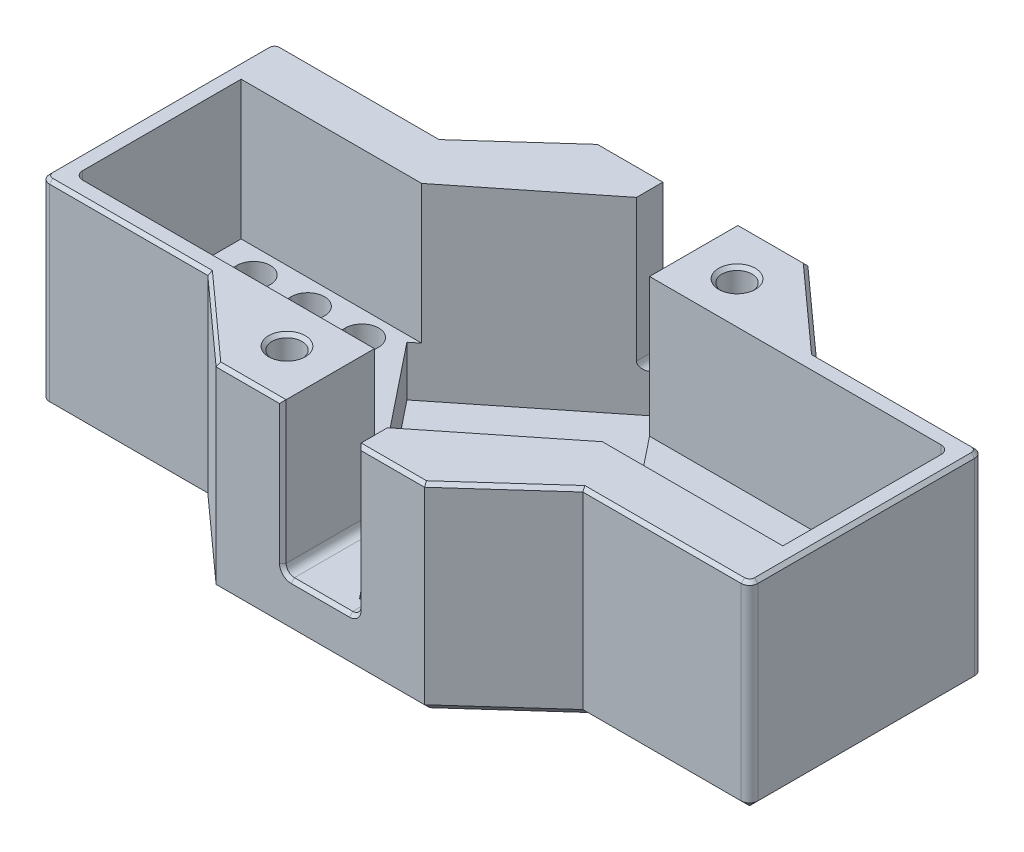
SolidWorks part; units mm, degrees
ref_plane "Front Plane" through (0, 0, 0) normal (0, 0, 1) x (1, 0, 0)
ref_plane "Top Plane" through (0, 0, 0) normal (0, 1, 0) x (1, 0, 0)
ref_plane "Right Plane" through (0, 0, 0) normal (1, 0, 0) x (0, 0, -1)
sketch "Sketch1" plane through (0, 0, 0) normal (0, 1, 0) x (1, 0, 0)
  line L0 (0, 47.9731) -> (0, -55.4983) construction
  line L1 (-64.8003, 0) -> (65.8454, 0) construction
  line L3 (-41.5, 14) -> (41.5, 14)
  line L4 (-42.5, 13) -> (-42.5, -13)
  line L5 (-41.5, -14) -> (41.5, -14)
  line L6 (42.5, 13) -> (42.5, -13)
  arc A0 (41.5, 14) -> (42.5, 13) centre (41.5, 13) cw
  arc A1 (41.5, -14) -> (42.5, -13) centre (41.5, -13) ccw
  arc A2 (-42.5, -13) -> (-41.5, -14) centre (-41.5, -13) ccw
  arc A3 (-41.5, 14) -> (-42.5, 13) centre (-41.5, 13) ccw
  point P11 (42.5, 14)
  point P14 (42.5, -14)
  point P19 (-42.5, 14)
  point P32 (41.5, -11)
  dimension "D3" = 1
  dimension "D1" = 85
  dimension "D2" = 28
extrude "Boss-Extrude2" add sketch "Sketch1" along normal blind 18 and the other way blind 6
sketch "Sketch4" plane through (0, 0, 0) normal (0, 1, 0) x (1, 0, 0)
  line L0 (0, 54.1428) -> (0, -67.8993) construction
  line L1 (-64.1281, 0) -> (64.7051, 0) construction
  line L2 (-12.5, 23) -> (12.5, 23)
  line L3 (12.5, 23) -> (22.5, 14)
  line L4 (41.5, 14) -> (-41.5, 14) construction
  line L6 (-22.5, 14) -> (-12.5, 23)
  line L7 (-22.5, -14) -> (-12.5, -23)
  line L8 (-41.5, -14) -> (41.5, -14) construction
  line L9 (-12.5, -23) -> (12.5, -23)
  line L10 (12.5, -23) -> (22.5, -14)
  line L11 (-22.5, 14) -> (-22.5, -14)
  line L12 (22.5, -14) -> (22.5, 14)
  dimension "D1" = 45
  dimension "D2" = 25
  dimension "D3" = 23
extrude "Boss-Extrude3" add sketch "Sketch4" along normal blind 18 and the other way blind 6
sketch "Sketch5" plane through (0, 0, 0) normal (0, 1, 0) x (1, 0, 0)
  line L1 (-40.5, 8) -> (-40.5, -11.0189)
  line L3 (40.4951, 10.9915) -> (40.4951, -8)
  line L4 (0, 34.3728) -> (0, -34.2865) construction
  line L5 (-53.6508, 0) -> (61.9313, 0) construction
  line L6 (-40.5, 8) -> (-13.5, 8)
  line L7 (-13.5, 8) -> (-13.5, 12)
  line L8 (13.4951, -12) -> (13.4951, -8)
  line L9 (13.4951, -8) -> (40.4951, -8)
  line L10 (-39.5189, -12) -> (13.4951, -12)
  line L11 (-13.5, 12) -> (39.477, 12)
  arc A0 (39.477, 12) -> (40.4951, 10.9915) centre (39.4866, 10.9915) cw
  arc A2 (-40.5, -11.0189) -> (-39.5189, -12) centre (-39.5189, -11.0189) ccw
  point P3 (0, 0)
  point P4 (-18.3724, 10.1)
  point P5 (0, 0)
  point P6 (0, 0)
  point P10 (0, 0)
  dimension "D1" = 12
  dimension "D2" = 80.9951
  dimension "D3" = 24
  dimension "D4" = 4
  dimension "D5" = 4
  dimension "D6" = 27
  dimension "D7" = 27
sketch "Sketch2" plane through (0, 0, 0) normal (0, 0, 1) x (1, 0, 0)
  line L0 (0, 26.5192) -> (0, -25.5049) construction
  line L1 (-24.2779, -6) -> (28.8134, -6) construction
  line L2 (-41.5, -6) -> (-22.5, -6) construction
  line L6 (-3.5, 19) -> (3.5, 19)
  line L9 (-4.5, 18) -> (-4.5, 1)
  line L10 (-3.5, 0) -> (3.5, 0)
  line L11 (4.5, 18) -> (4.5, 1)
  arc A4 (3.5, 0) -> (4.5, 1) centre (3.5, 1) ccw
  arc A5 (-4.5, 1) -> (-3.5, 0) centre (-3.5, 1) ccw
  arc A6 (3.5, 19) -> (4.5, 18) centre (3.5, 18) cw
  arc A7 (-3.5, 19) -> (-4.5, 18) centre (-3.5, 18) ccw
  point P19 (0, 0)
  dimension "D1" = 1
  dimension "D2" = 9
  dimension "D3" = 19
  dimension "D4" = 6
extrude "load bar arm slots" cut sketch "Sketch2" against normal blind 30 and the other way blind 30 contours L9 A5 L10 A4 L11 A6 L6 A7
extrude "10kg TAL bar slot" cut sketch "Sketch5" along normal up to vertex (18 mm away) from offset 1.4 up to point (-41.5, 18, 14)
sketch "Sketch3" plane through (0, 0, 0) normal (0, 1, 0) x (1, 0, 0)
  line L0 (0, 44.5647) -> (0, -57.8829) construction
  line L1 (-55.4498, 0) -> (55.4498, 0) construction
  line L2 (-2.6223, 20.9314) -> (-19.8228, 7.2149)
  line L3 (-19.8228, 7.2149) -> (2.6223, -20.9314)
  line L4 (2.6223, -20.9314) -> (19.8228, -7.2149)
  line L5 (19.8228, -7.2149) -> (-2.6223, 20.9314)
  line L6 (-8.6003, -6.8582) -> (8.6003, 6.8582) construction
  line L7 (-11.2226, 14.0732) -> (11.2226, -14.0732) construction
  point P13 (-4.5, -12)
  point P17 (4.5, 12)
  point P22 (0, 0)
  dimension "D1" = 22
  dimension "D2" = 36
extrude "hx711 chip holster" cut sketch "Sketch3" against normal offset from surface 1.4 and the other way up to vertex (18 mm away) contours L3 L4 L5 L2 up to face at (0, -6, 0) other way up to point (-41.5, 18, 14)
sketch "Sketch6" plane through (0, 0, 0) normal (0, 1, 0) x (1, 0, 0)
  line L0 (0, 33.6156) -> (0, -37.2618) construction
  line L1 (-46.4216, 0) -> (49.9788, 0) construction
  circle A0 centre (-10, -17) radius 1.8
  circle A1 centre (10, 17) radius 1.8
  point P9 (0, 0)
  point P10 (0, 0)
  dimension "D5" = 3.6
  dimension "D1" = 10
  dimension "D2" = 10
  dimension "D3" = 17
  dimension "D4" = 17
extrude "screw hole" cut sketch "Sketch6" along normal up to vertex (18 mm away) up to point (-41.5, 18, 14)
chamfer "Chamfer3" distance 0.4 angle 45 30 edges at (-17.5, 18, -18.5) (-8.5, 18, -23) (-4.5, 9.5, -23) (-4.2071, 0.2929, -23) (0, 0, -23) (4.2071, 0.2929, -23) (4.5, 9.5, -23) (8.5, 18, -23) (17.5, 18, -18.5) (32, 18, -14) (42.2071, 18, -13.7071) (42.5, 18, 0) (42.2071, 18, 13.7071) (32, 18, 14) (17.5, 18, 18.5) (8.5, 18, 23) (4.5, 9.5, 23) (4.2071, 0.2929, 23) (0, 0, 23) (-4.2071, 0.2929, 23) (-4.5, 9.5, 23) (-8.5, 18, 23) (-17.5, 18, 18.5) (-32, 18, 14) (-42.2071, 18, 13.7071) (-32, 18, -14) (-42.2071, 18, -13.7071) (-42.5, 18, 0) (10, 18, -15.2) (-10, 18, 18.8)
chamfer "Chamfer8" distance 1 angle 45 16 edges at (-42.2071, -6, -13.7071) (-42.5, -6, 0) (-42.2071, -6, 13.7071) (-32, -6, 14) (-17.5, -6, 18.5) (0, -6, 23) (17.5, -6, 18.5) (32, -6, 14) (42.2071, -6, 13.7071) (42.5, -6, 0) (42.2071, -6, -13.7071) (32, -6, -14) (17.5, -6, -18.5) (0, -6, -23) (-17.5, -6, -18.5) (-32, -6, -14)
sketch "Sketch10" plane through (0, 0, 0) normal (0, 1, 0) x (1, 0, 0)
  line L0 (0, 27.422) -> (0, -31.3035) construction
  line L1 (-47.728, 0) -> (55.5628, 0) construction
  line L2 (-36, -5) -> (-36, 5) construction
  line L3 (-38, -5) -> (-38, 5)
  line L4 (-34, -5) -> (-34, 5)
  line L5 (-29.5, -5) -> (-29.5, 5) construction
  line L6 (-31.5, -5) -> (-31.5, 5)
  line L7 (-27.5, -5) -> (-27.5, 5)
  line L8 (-23, -5) -> (-23, 5) construction
  line L9 (-25, -5) -> (-25, 5)
  line L10 (-21, -5) -> (-21, 5)
  line L11 (23, -5) -> (23, 5) construction
  line L12 (21, -5) -> (21, 5)
  line L13 (25, -5) -> (25, 5)
  line L14 (29.5, -5) -> (29.5, 5) construction
  line L15 (27.5, -5) -> (27.5, 5)
  line L16 (31.5, -5) -> (31.5, 5)
  line L17 (36, -5) -> (36, 5) construction
  line L18 (34, -5) -> (34, 5)
  line L19 (38, -5) -> (38, 5)
  arc A0 (-38, -5) -> (-34, -5) centre (-36, -5) ccw
  arc A1 (-34, 5) -> (-38, 5) centre (-36, 5) ccw
  arc A2 (-31.5, -5) -> (-27.5, -5) centre (-29.5, -5) ccw
  arc A3 (-27.5, 5) -> (-31.5, 5) centre (-29.5, 5) ccw
  arc A4 (-25, -5) -> (-21, -5) centre (-23, -5) ccw
  arc A5 (-21, 5) -> (-25, 5) centre (-23, 5) ccw
  arc A6 (21, -5) -> (25, -5) centre (23, -5) ccw
  arc A7 (25, 5) -> (21, 5) centre (23, 5) ccw
  arc A8 (27.5, -5) -> (31.5, -5) centre (29.5, -5) ccw
  arc A9 (31.5, 5) -> (27.5, 5) centre (29.5, 5) ccw
  arc A10 (34, -5) -> (38, -5) centre (36, -5) ccw
  arc A11 (38, 5) -> (34, 5) centre (36, 5) ccw
  point P7 (-36, 0)
  point P13 (-29.5, 0)
  point P20 (-23, 0)
  point P27 (23, 0)
  point P34 (29.5, 0)
  point P41 (36, 0)
  point P47 (0, 0)
  point P48 (0, 0)
  point P49 (0, 0)
  dimension "D2" = 2
  dimension "D1" = 10
  dimension "D3" = 6.5
  dimension "D4" = 6.5
  dimension "D5" = 36
extrude "Cut-Extrude6" cut sketch "Sketch10" against normal blind 7 and the other way blind 7
